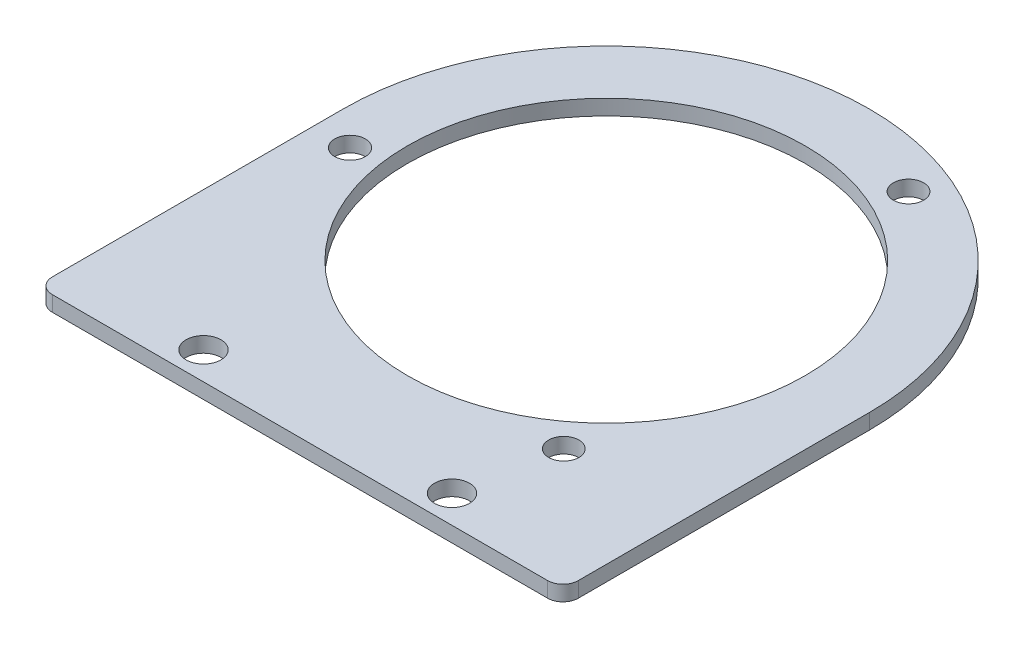
SolidWorks part; units mm, degrees
ref_plane "Front Plane" through (0, 0, 0) normal (0, 0, 1) x (1, 0, 0)
ref_plane "Top Plane" through (0, 0, 0) normal (0, 1, 0) x (1, 0, 0)
ref_plane "Right Plane" through (0, 0, 0) normal (1, 0, 0) x (0, 0, -1)
sketch "Sketch4" plane through (0, 0, 0) normal (0, 1, 0) x (1, 0, 0)
  line L0 (-102.6827, -127) -> (102.6827, -127)
  line L1 (109.0327, -120.65) -> (109.0327, 0)
  line L2 (-109.0327, 0) -> (-109.0327, -120.65)
  line L3 (-51.5149, -115.4874) -> (-51.5149, -127) construction
  line L4 (0, -116.8469) -> (0, -105.3343) construction
  arc A0 (-109.0327, 0) -> (109.0327, 0) centre (0, 0) cw
  circle A1 centre (0, 0) radius 82.4943
  circle A2 centre (-51.5149, -115.4874) radius 7.2466
  circle A3 centre (51.5149, -115.4874) radius 7.2466
  arc A5 (102.6827, -127) -> (109.0327, -120.65) centre (102.6827, -120.65) ccw
  arc A6 (-102.6827, -127) -> (-109.0327, -120.65) centre (-102.6827, -120.65) cw
  circle A8 centre (-93.6824, -12.5611) radius 6.3519
  circle A11 centre (37.8028, 87.5005) radius 6.2835
  circle A12 centre (58.6974, -76.3199) radius 6.2784
  point P19 (-109.0327, -127)
  point P22 (109.0327, -127)
  point P30 (0, 0)
  dimension "D4" = 14.4933
  dimension "D5" = 164.9886
  dimension "D8" = 6.35
  dimension "D1" = 127
  dimension "D2" = 218.0654
  dimension "D3" = 51.5149
  dimension "D6" = 11.5126
extrude "Boss-Extrude1" add sketch "Sketch4" along normal blind 6.35 contours L0 A5 L1 A0 L2 A6 | A1 | A3 | A2 | A8 | A12 | A11
